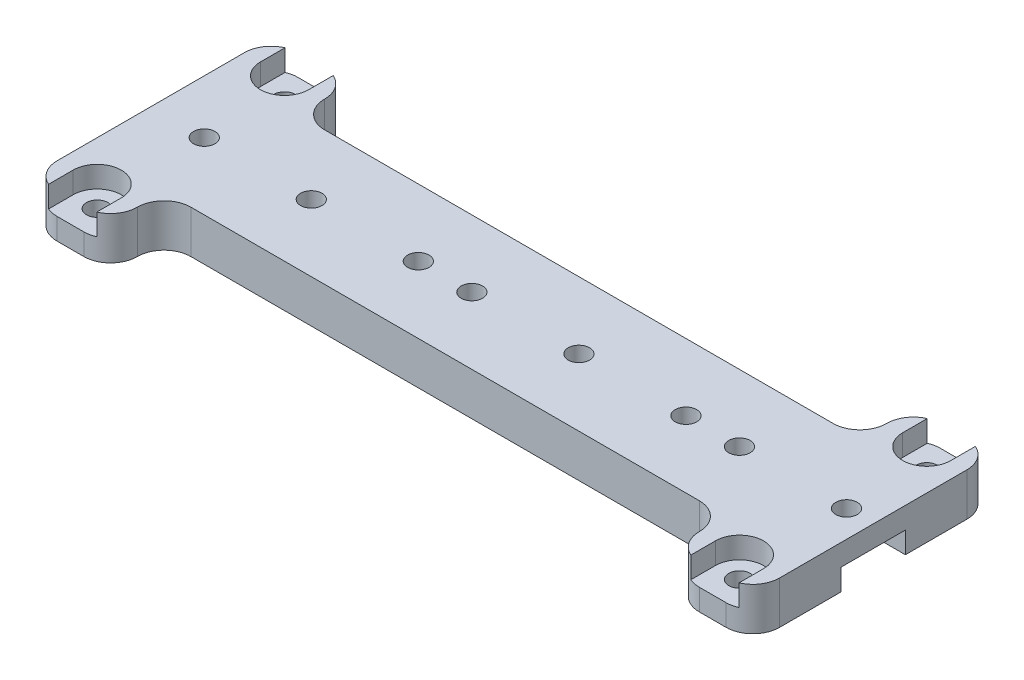
SolidWorks part; units mm, degrees
ref_plane "Front Plane" through (0, 0, 0) normal (0, 0, 1) x (1, 0, 0)
ref_plane "Top Plane" through (0, 0, 0) normal (0, 1, 0) x (1, 0, 0)
ref_plane "Right Plane" through (0, 0, 0) normal (1, 0, 0) x (0, 0, -1)
sketch "Sketch1" plane through (0, 0, 0) normal (0, 1, 0) x (1, 0, 0)
  line L0 (-10, 35) -> (145, 35)
  line L1 (0, 0) -> (135, 0)
  line L2 (0, 0) -> (0, 25)
  line L3 (0, 25) -> (135, 25)
  line L4 (135, 0) -> (135, 25)
  line L5 (145, -10) -> (145, 35)
  line L6 (-10, -10) -> (145, -10)
  line L7 (-10, -10) -> (-10, 35)
  dimension "D1" = 135
  dimension "D2" = 25
  dimension "D3" = 10
extrude "Boss-Extrude1" add sketch "Sketch1" along normal blind 8 contours L1 L4 L3 L2 | L0 L5 L6 L7
sketch "Sketch2" plane through (0, 8, 0) normal (0, 1, 0) x (1, 0, 0)
  line L1 (0, 25) -> (15, 25)
  line L2 (0, 25) -> (0, 35)
  line L3 (0, 35) -> (15, 35)
  line L4 (15, 25) -> (15, 35)
  dimension "D1" = 10
  dimension "D2" = 15
ref_plane "Plane1" through (67.5, 0, 0) normal (-1, 0, 0) x (0, 0, 1)
ref_plane "Plane2" through (0, 0, -12.5) normal (0, 0, 1) x (1, 0, 0)
extrude "Boss-Extrude2" add sketch "Sketch2" against normal up to surface (8 mm away) up to face at (67.5, 0, -12.5)
fillet "Fillet1" radius 5 2 edges at (15, 4, -35) (0, 4, -35)
sketch "Sketch3" plane through (0, 8, 0) normal (0, 1, 0) x (1, 0, 0)
  line L0 (15, 25) -> (0, 25) construction
  line L1 (0, 25) -> (7.5, 25) construction
  line L2 (7.5, 25) -> (7.5, 35) construction
  line L3 (-10, 35) -> (145, 35) construction
  circle A0 centre (7.5, 30) radius 2
  dimension "D1" = 4
extrude "Cut-Extrude1" cut sketch "Sketch3" against normal blind 10
sketch "Sketch4" plane through (0, 8, 0) normal (0, 1, 0) x (1, 0, 0)
  line L0 (3, 30) -> (3, 34.5826)
  line L1 (3, 34.5826) -> (3.7513, 37.1395)
  line L2 (3.7513, 37.1395) -> (12, 36.5322)
  line L3 (12, 36.5322) -> (12, 30)
  arc A0 (3, 30) -> (12, 30) centre (7.5, 30) ccw
  arc A1 (5, 35) -> (0, 30) centre (5, 30) ccw construction
  dimension "D1" = 9
extrude "Cut-Extrude2" cut sketch "Sketch4" against normal blind 4
mirror "Mirror3" about plane through (0, 0, -12.5) normal (0, 0, 1) of "Cut-Extrude2", "Cut-Extrude1", "Boss-Extrude2" second plane through (67.5, 0, 0) second plane normal (-1, 0, 0)
fillet "Fillet2" radius 5 36 edges at (133.4387, 8, -35) (131.8773, 6, -35) (123, 6, -35) (131.9387, 8, -34.7913) (131.9387, 4, -34.7913) (1.5613, 8, 10) (3.1227, 6, 10) (12, 6, 10) (3.0613, 8, 9.7913) (3.0613, 4, 9.7913) (133.4387, 8, 10) (123, 6, 10) (131.8773, 6, 10) (15, 4, -25) (131.9387, 8, 9.7913) (131.9387, 4, 9.7913) (15, 8, -27.5) (15, 0, -27.5) (120, 4, -35) (121.5, 8, -35) (120, 0, -30) (120, 4, -25) (120, 8, -30) (135, 4, -35) (15, 4, 10) (13.5, 8, 10) (15, 0, 5) (15, 4, 0) (15, 8, 5) (0, 4, 10) (135, 4, 10) (120, 4, 10) (120, 4, 0) (120, 8, 5) (121.5, 8, 10) (120, 0, 5)
sketch "Sketch5" plane through (0, 8, 0) normal (0, 1, 0) x (1, 0, 0)
  line L0 (0, 12.5) -> (135, 12.5) construction
  line L1 (0, 0) -> (0, 25) construction
  line L2 (135, 0) -> (135, 25) construction
  circle A0 centre (10, 12.5) radius 2
  circle A1 centre (20, 12.5) radius 2 [skipped]
  circle A2 centre (30, 12.5) radius 2
  circle A3 centre (40, 12.5) radius 2 [skipped]
  circle A4 centre (50, 12.5) radius 2
  circle A5 centre (60, 12.5) radius 2
  circle A6 centre (70, 12.5) radius 2 [skipped]
  circle A7 centre (80, 12.5) radius 2
  circle A8 centre (90, 12.5) radius 2 [skipped]
  circle A9 centre (100, 12.5) radius 2
  circle A10 centre (110, 12.5) radius 2
  circle A11 centre (120, 12.5) radius 2 [skipped]
  circle A12 centre (130, 12.5) radius 2
  dimension "D1" = 4
  dimension "D2" = 10
  dimension "D3" = 13
extrude "Cut-Extrude3" cut sketch "Sketch5" against normal blind 10
sketch "Sketch6" plane through (0, 0, 0) normal (0, -1, 0) x (1, 0, 0)
  line L0 (135, -12.5) -> (0, -12.5) construction
  line L1 (135, 0) -> (135, -25) construction
  line L2 (0, 0) -> (0, -25) construction
  line L3 (135, -6.5) -> (0, -6.5)
  line L4 (0, -6.5) -> (0, -18.5)
  line L5 (0, -18.5) -> (135, -18.5)
  line L6 (135, -18.5) -> (135, -6.5)
  dimension "D1" = 6
  dimension "D2" = 6
extrude "Cut-Extrude4" cut sketch "Sketch6" against normal blind 4
